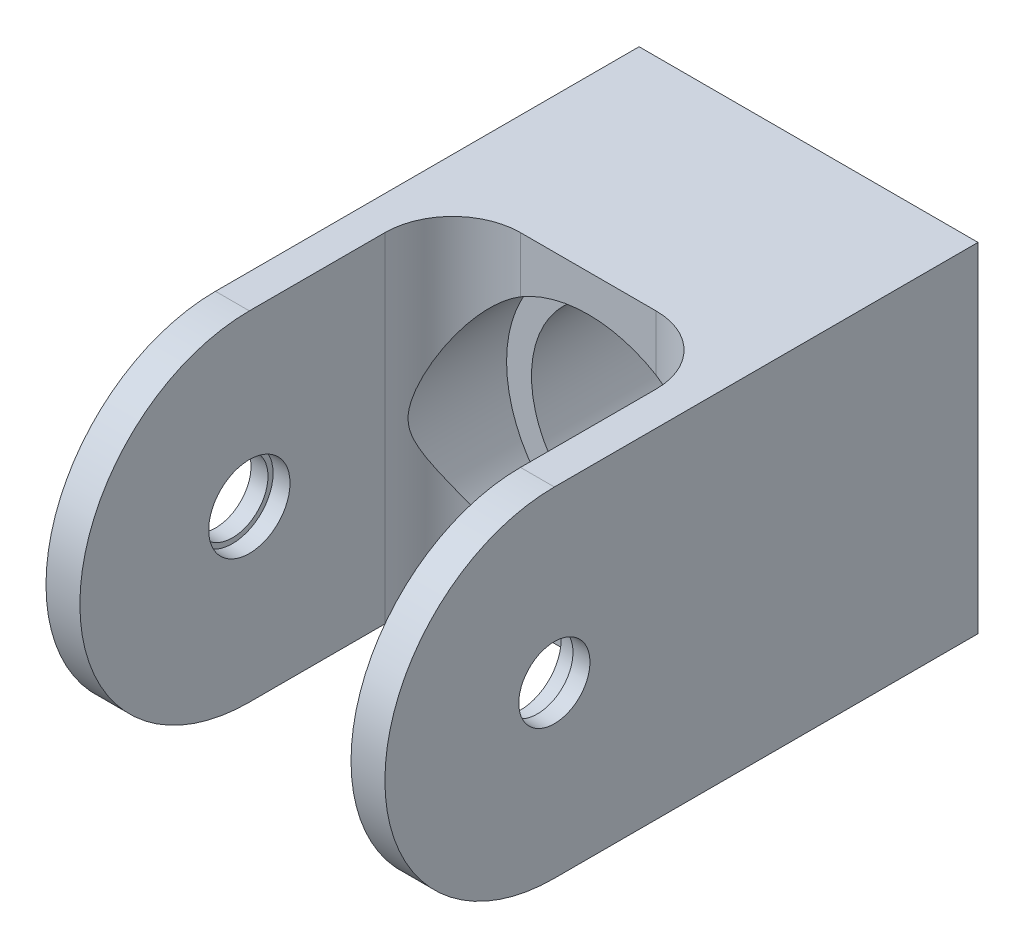
SolidWorks part; units mm, degrees
ref_plane "Front Plane" through (0, 0, 0) normal (0, 0, 1) x (1, 0, 0)
ref_plane "Top Plane" through (0, 0, 0) normal (0, 1, 0) x (1, 0, 0)
ref_plane "Right Plane" through (0, 0, 0) normal (1, 0, 0) x (0, 0, -1)
sketch "Sketch1" plane through (0, 0, 0) normal (0, 0, 1) x (1, 0, 0)
  circle A2 centre (0, 0) radius 31.75
  circle A4 centre (0, 0) radius 39.1
  circle A5 centre (0, 0) radius 38.1 construction
  dimension "D1" = 1
  dimension "D2" = 63.5
extrude "Centre Hole for L2" add sketch "Sketch1" along normal blind 40 and the other way blind 10 contours A4 | A2
sketch "Sketch2" plane through (0, 0, 40) normal (0, 0, 1) x (1, 0, 0)
  line L0 (0, 48.4974) -> (0, 0) construction
  line L5 (-50, 50) -> (-50, -50)
  line L12 (0, 0) -> (72.986, 0) construction
  line L16 (-50, 50) -> (50, 50)
  line L17 (50, 50) -> (50, -50)
  line L18 (-50, -50) -> (50, -50)
  circle A2 centre (0, 0) radius 39.1
  circle A3 centre (0, 0) radius 39.1 construction
  point P9 (0, 0)
  point P10 (0, 0)
  point P11 (0, 0)
  point P13 (0, 50)
  point P15 (0, 0)
  dimension "D1" = 50
  dimension "D2" = 100
extrude "Main Structure" add sketch "Sketch2" along normal blind 75 and the other way blind 50 separate body contours L5 L18 L17 L16 A2
sketch "Sketch3" plane through (-50, 0, 0) normal (-1, 0, 0) x (0, 0, 1)
  line L0 (115, 50) -> (115, -50) construction
  line L1 (115, 50) -> (115, -50)
  line L2 (-10, 50) -> (115, 50) construction
  line L3 (-10, -50) -> (115, -50) construction
  line L4 (-10, 50) -> (115, 50) construction
  arc A0 (115, 50) -> (115, -50) centre (115, 0) cw
extrude "Bearing Curve" add sketch "Sketch3" against normal blind 10 contours A0 L1
mirror "Upright Mirror" about plane through (0, 0, 0) normal (1, 0, 0) of "Bearing Curve"
sketch "Sketch6" plane through (-50, 0, 0) normal (-1, 0, 0) x (0, 0, 1)
  circle A0 centre (115, 0) radius 10.5
  dimension "D1" = 21
extrude "Shaft Hole" cut sketch "Sketch6" against normal up to surface (10 mm away) up to face at (-40, 0, 140)
sketch "Sketch4" plane through (0, 50, 0) normal (0, 1, 0) x (1, 0, 0)
  line L0 (0, -115) -> (0, 10) construction
  line L3 (-40, -115) -> (-40, -75)
  line L6 (40, -115) -> (40, -75)
  line L7 (-50, 10) -> (50, 10) construction
  line L8 (-40, -115) -> (40, -115) construction
  line L9 (-20, -55) -> (20, -55)
  line L10 (-40, -115) -> (40, -115)
  arc A0 (-40, -75) -> (-20, -55) centre (-20, -75) cw
  arc A1 (40, -75) -> (20, -55) centre (20, -75) ccw
  point P17 (0, -115)
  dimension "D2" = 20
  dimension "D1" = 65
extrude "Wrist Cutout" cut sketch "Sketch4" against normal through all
sketch "Sketch9" plane through (-40, 0, 0) normal (1, 0, 0) x (0, 0, -1)
  circle A0 centre (-115, 0) radius 12
  dimension "D1" = 24
extrude "Bearing" cut sketch "Sketch9" against normal blind 5
mirror "Bearing Mirror" about plane through (0, 0, 0) normal (1, 0, 0) of "Bearing", "Shaft Hole"
